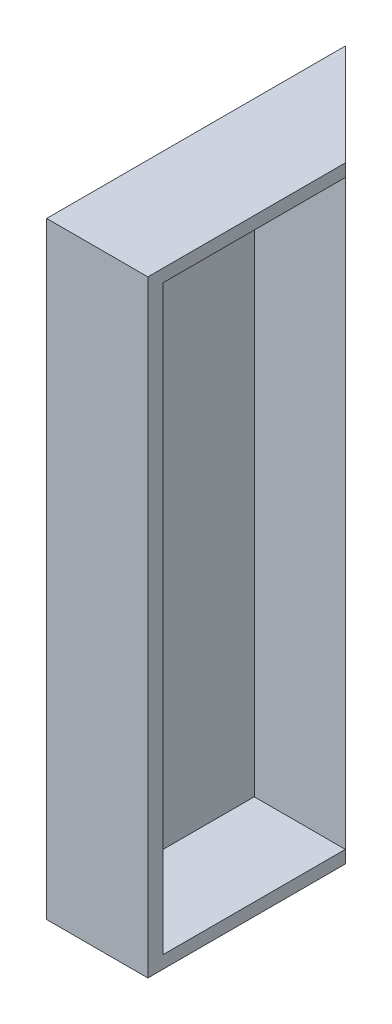
SolidWorks part; units mm, degrees
ref_plane "Front Plane" through (0, 0, 0) normal (0, 0, 1) x (1, 0, 0)
ref_plane "Top Plane" through (0, 0, 0) normal (0, 1, 0) x (1, 0, 0)
ref_plane "Right Plane" through (0, 0, 0) normal (1, 0, 0) x (0, 0, -1)
sketch "Sketch2" plane through (0, 0, 0) normal (0, 1, 0) x (1, 0, 0)
  line L14 (-22, -22) -> (-22, -12)
  line L15 (-22, -12) -> (-12, -22)
  line L16 (-12, -22) -> (-22, -22)
  point P26 (0, -0.2913)
  point P27 (0, 0)
  dimension "D3" = 10
extrude "Boss-Extrude1" add sketch "Sketch2" along normal blind 60 contours L16 L15 L14 region at (-18.6667, 0, 18.6667)
ref_plane "Plane1" through (-12, 60, 22) normal (0.7071, 0, 0.7071) x (0.7071, 0, -0.7071)
sketch "Sketch4" plane through (0, 0, 0) normal (0, -1, 0) x (1, 0, 0)
  line L0 (-9.25, 19.25) -> (-14.75, 24.75) construction
  line L1 (-12, 22) -> (-22, 22)
  line L2 (-12, 22) -> (-12, 41.5123)
  line L3 (-12, 41.5123) -> (-22, 41.5123)
  line L5 (-22, 12) -> (-12, 22) construction
  line L6 (-22, 22) -> (-22, 41.5123)
  line L8 (-12, 41.5123) -> (-22, 41.5123)
  line L9 (-12, 41.5123) -> (-12, 40.0146)
  line L10 (-12, 40.0146) -> (-22, 40.0146)
  line L11 (-22, 41.5123) -> (-22, 40.0146)
extrude "Boss-Extrude2" add sketch "Sketch4" against normal up to surface (60 mm away) separate body contours L9 L8 L11 L10 up to face at (-18.6667, 60, 18.6667)
sketch "Sketch6" plane through (0, 0, 0) normal (0, -1, 0) x (-1, 0, 0)
  line L1 (22, -22) -> (12, -22)
  line L2 (22, -22) -> (22, -40.0146)
  line L3 (22, -40.0146) -> (12, -40.0146)
  line L4 (12, -22) -> (12, -40.0146)
extrude "Boss-Extrude3" add sketch "Sketch6" against normal blind 5
ref_plane "Plane2" through (0, 0, 31.0073) normal (0, 0, -1) x (-1, 0, 0)
ref_plane "Plane3" through (0, 30, 0) normal (0, 1, 0) x (1, 0, 0)
mirror "Mirror1" about plane through (0, 30, 0) normal (0, 1, 0) of "Boss-Extrude3"
sketch "Sketch7" plane through (-12, 0, 0) normal (1, 0, 0) x (0, 0, -1)
  line L0 (-22, 55) -> (-22, 57.5)
  line L1 (-22, 60) -> (-22, 55) construction
  line L3 (-40.0146, 55) -> (-40.0146, 57.5)
  line L5 (-22, 55) -> (-40.0146, 55)
  line L6 (-22, 5) -> (-22, 2.5)
  line L7 (-22, 5) -> (-22, 0) construction
  line L9 (-40.0106, 2.5) -> (-40.0146, 5)
  line L10 (-40.0146, 5) -> (-22, 5)
  line L11 (-40.0106, 2.5) -> (-40.0106, 1.25)
  line L12 (-40.0106, 1.25) -> (-22, 1.25)
  line L13 (-22, 1.25) -> (-22, 2.5)
  line L14 (-40.0146, 57.5) -> (-40.0146, 58.75)
  line L15 (-40.0146, 58.75) -> (-22, 58.75)
  line L16 (-22, 58.75) -> (-22, 57.5)
  line M17 (-22, 0) -> (-22, 5)
  line M18 (-22, 5) -> (-40.0146, 5)
  line M20 (-40.0146, 55) -> (-22, 55)
  line M21 (-22, 55) -> (-22, 60)
extrude "Cut-Extrude1" cut sketch "Sketch7" against normal up to surface (10 mm away) contours L15 L14 L3 M20 M21 | L11 L12 L9 M17 M18 region at (-12, 56.875, 31.0073) region at (-12, 3.1251, 31.006) up to face at (-22, 30, 31.0073)
sketch "Sketch8" plane through (-22, 0, 0) normal (-1, 0, 0) x (0, 0, 1)
  line L1 (22, 58.75) -> (40.0106, 58.75)
  line L2 (22, 58.75) -> (22, 1.25)
  line L3 (22, 1.25) -> (40.0106, 1.25)
  line L4 (40.0106, 58.75) -> (40.0106, 1.25)
extrude "Boss-Extrude4" add sketch "Sketch8" against normal blind 1
